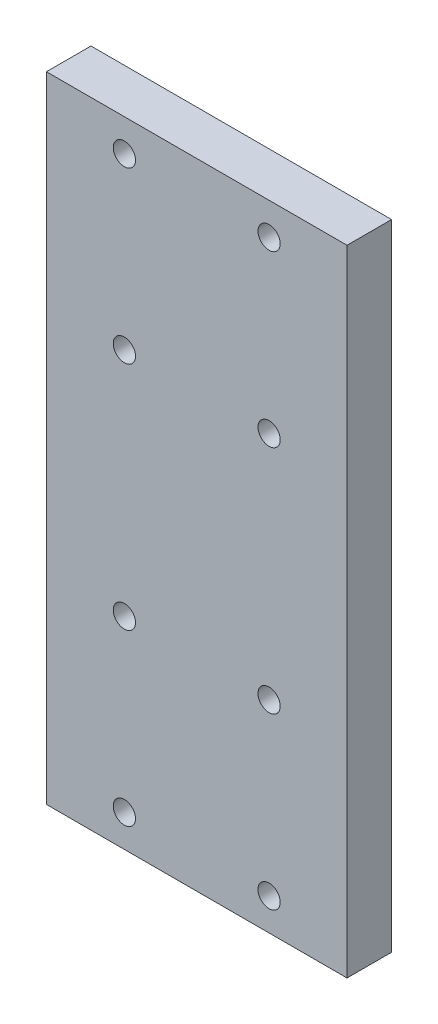
SolidWorks part; units mm, degrees
ref_plane "Front Plane" through (0, 0, 0) normal (0, 0, 1) x (1, 0, 0)
ref_plane "Top Plane" through (0, 0, 0) normal (0, 1, 0) x (1, 0, 0)
ref_plane "Right Plane" through (0, 0, 0) normal (1, 0, 0) x (0, 0, -1)
sketch "Sketch1" plane through (0, 0, 0) normal (0, 0, 1) x (1, 0, 0)
  line L0 (0, 57) -> (0, -57) construction
  line L1 (-27, -57) -> (27, -57)
  line L2 (-27, -57) -> (-27, 57)
  line L3 (-27, 57) -> (27, 57)
  line L4 (27, -57) -> (27, 57)
  line L5 (-27, -57) -> (27, 57) construction
  line L6 (-27, 57) -> (27, -57) construction
  line L7 (-27, -35.97) -> (0, -35.97) construction
  line L8 (-27, 35.97) -> (0, 35.97) construction
  line L10 (-13, 20.72) -> (13, 20.72) construction
  line L11 (-13, 20.72) -> (-13, 51.22) construction
  line L12 (-13, 51.22) -> (13, 51.22) construction
  line L13 (13, 20.72) -> (13, 51.22) construction
  line L14 (-13, 20.72) -> (13, 51.22) construction
  line L15 (-13, 51.22) -> (13, 20.72) construction
  line L16 (-13, -51.22) -> (13, -51.22) construction
  line L17 (-13, -51.22) -> (-13, -20.72) construction
  line L18 (-13, -20.72) -> (13, -20.72) construction
  line L19 (13, -51.22) -> (13, -20.72) construction
  line L20 (-13, -51.22) -> (13, -20.72) construction
  line L21 (-13, -20.72) -> (13, -51.22) construction
  circle A0 centre (-13, 51.22) radius 2
  circle A1 centre (13, 51.22) radius 2
  circle A2 centre (13, 20.72) radius 2
  circle A3 centre (-13, 20.72) radius 2
  circle A4 centre (13, -20.72) radius 2
  circle A5 centre (-13, -20.72) radius 2
  circle A6 centre (-13, -51.22) radius 2
  circle A7 centre (13, -51.22) radius 2
  point P0 (0, 0)
  dimension "D1" = 114
  dimension "D2" = 54
  dimension "D3" = 35.97
  dimension "D4" = 35.97
  dimension "D5" = 26
  dimension "D6" = 30.5
  dimension "D7" = 26
  dimension "D8" = 30.5
extrude "Boss-Extrude1" add sketch "Sketch1" along normal blind 8
